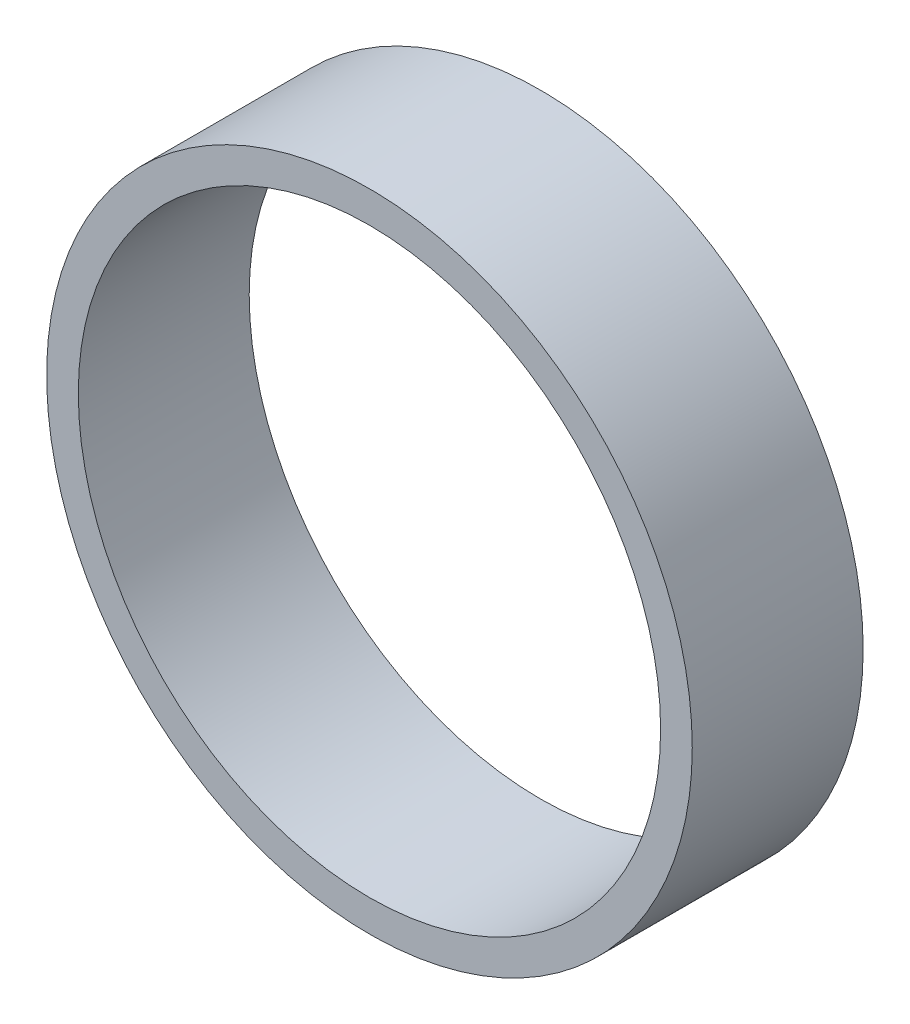
SolidWorks part; units mm, degrees
ref_plane "Front Plane" through (0, 0, 0) normal (0, 0, 1) x (1, 0, 0)
ref_plane "Top Plane" through (0, 0, 0) normal (0, 1, 0) x (1, 0, 0)
ref_plane "Right Plane" through (0, 0, 0) normal (1, 0, 0) x (0, 0, -1)
sketch "Sketch1" plane through (0, 0, 0) normal (0, 0, 1) x (1, 0, 0)
  circle A0 centre (0, 0) radius 46
  circle A1 centre (0, 0) radius 51
  dimension "D1" = 92
  dimension "D2" = 5
extrude "Boss-Extrude1" add sketch "Sketch1" along normal blind 27
